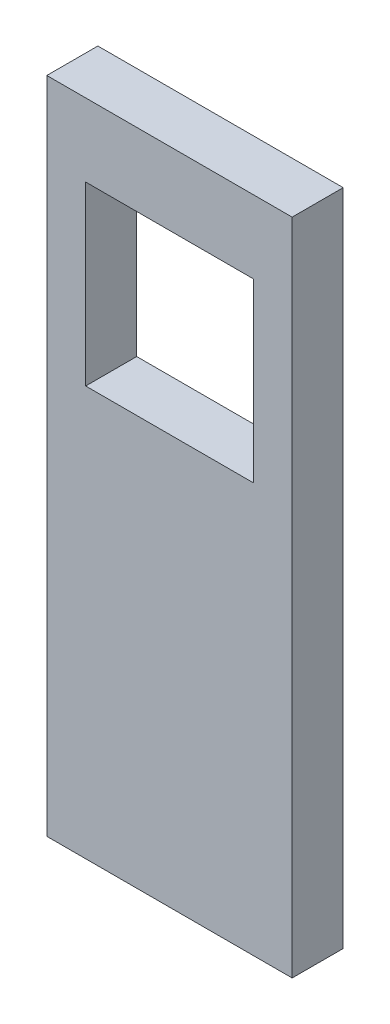
SolidWorks part; units mm, degrees
ref_plane "Front Plane" through (0, 0, 0) normal (0, 0, 1) x (1, 0, 0)
ref_plane "Top Plane" through (0, 0, 0) normal (0, 1, 0) x (1, 0, 0)
ref_plane "Right Plane" through (0, 0, 0) normal (1, 0, 0) x (0, 0, -1)
sketch "Sketch1" plane through (0, 0, 0) normal (0, 0, 1) x (1, 0, 0)
  line L0 (0, 67.15) -> (0, 44.75)
  line L1 (0, 67.15) -> (25, 67.15)
  line L2 (0, 44.75) -> (0, 39.55)
  line L3 (25, 0) -> (0, 0)
  line L4 (3.96, 59.725) -> (21.04, 59.725)
  line L5 (3.96, 41.725) -> (21.04, 41.725)
  line L6 (3.96, 59.725) -> (3.96, 41.725)
  line L7 (21.04, 59.725) -> (21.04, 41.725)
  line L8 (0, 44.75) -> (25, 44.75) construction
  line L9 (0, 39.55) -> (25, 39.55) construction
  line L10 (0, 39.55) -> (0, 27.6)
  line L11 (0, 27.6) -> (0, 22.4)
  line L12 (25, 44.75) -> (25, 39.55)
  line L13 (25, 67.15) -> (25, 44.75)
  line L14 (0, 22.4) -> (0, 0)
  line L15 (25, 39.55) -> (25, 27.6)
  line L16 (25, 27.6) -> (25, 22.4)
  line L17 (25, 22.4) -> (25, 0)
  line L18 (0, 27.6) -> (25, 27.6) construction
  line L19 (25, 22.4) -> (0, 22.4) construction
  line L20 (12.5, -0.0005) -> (12.5, 4.0956) construction
  point P18 (12.5, 41.725)
  point P20 (12.5, 59.725)
  point P21 (12.5, 67.15)
  dimension "D1" = 3.025
  dimension "D2" = 11.95
  dimension "D3" = 5.2
  dimension "D4" = 25
  dimension "D5" = 18
  dimension "D6" = 17.08
  dimension "D7" = 22.4
extrude "Boss-Extrude1" add sketch "Sketch1" along normal mid plane 5.2
